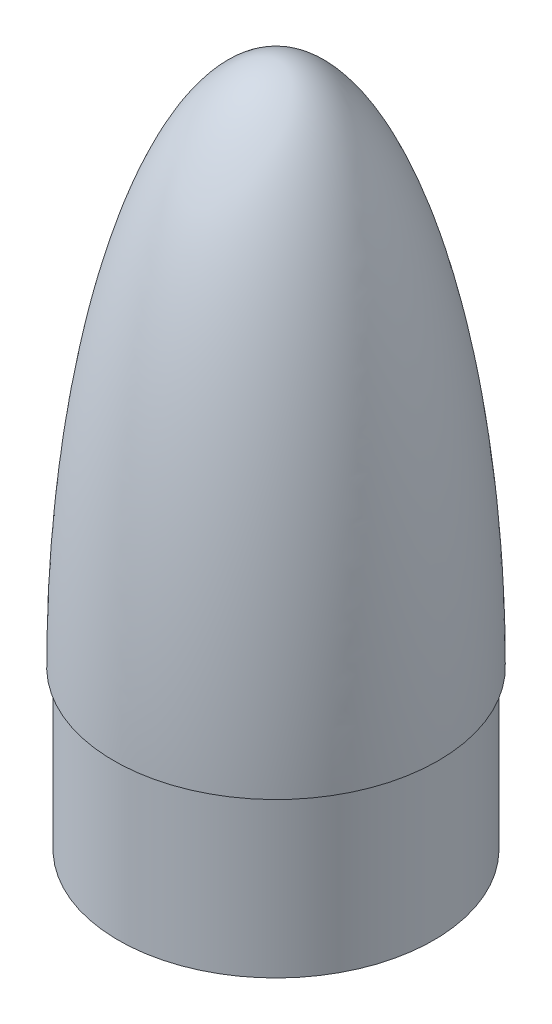
SolidWorks part; units mm, degrees
material "ABS"
ref_plane "Front Plane" through (0, 0, 0) normal (0, 0, 1) x (1, 0, 0)
ref_plane "Top Plane" through (0, 0, 0) normal (0, 1, 0) x (1, 0, 0)
ref_plane "Right Plane" through (0, 0, 0) normal (1, 0, 0) x (0, 0, -1)
sketch "Sketch1" plane through (0, 0, 0) normal (0, 0, 1) x (1, 0, 0)
  line L0 (0, 254) -> (0, 0) construction
  line L1 (78.359, 0) -> (0, 0)
  line L2 (0, 0) -> (0, 254)
  spline S0 degree 4 poles (77.9662, -25.3999) (78.0154, -23.8095) (78.1056, -20.6522) (78.1976, -16.6458) (78.2773, -11.9379) (78.3233, -7.8867) (78.3478, -4.9036) (78.3593, -1.4843) (78.3601, 0.7911) (78.3527, 3.5863) (78.3388, 5.9889) (78.318, 8.3522) (78.2903, 10.7456) (78.247, 13.7314) (78.1811, 17.3117) (78.0839, 21.4904) (77.9448, 26.2641) (77.7777, 31.0376) (77.5823, 35.8096) (77.3585, 40.5805) (77.0429, 46.5423) (76.6791, 52.5014) (76.2664, 58.4574) (75.8041, 64.4096) (75.404, 69.1689) (74.8656, 75.1148) (74.1574, 82.244) (73.2383, 90.5517) (72.0557, 100.0308) (70.7355, 109.4917) (69.2709, 118.9313) (67.25, 130.6999) (64.5017, 144.7638) (61.3086, 158.736) (57.591, 172.5772) (53.383, 186.2759) (49.2387, 198.0448) (44.4832, 209.5873) (38.9429, 220.7192) (34.2562, 228.6936) (29.8187, 235.0954) (25.6242, 240.1829) (21.9789, 243.9262) (18.5702, 246.8595) (15.4743, 249.0762) (12.5634, 250.7857) (9.7723, 252.0835) (7.0631, 253.0286) (4.2754, 253.6868) (2.188, 253.9399) (0.7672, 253.9999) (0, 254) knots 0 0 0 0 0 0.020823 0.041645 0.052056 0.062468 0.072879 0.08329 0.09112 0.098949 0.106779 0.114608 0.122438 0.130267 0.145926 0.161585 0.177244 0.192903 0.208562 0.224221 0.23988 0.271198 0.286857 0.302516 0.318175 0.333834 0.365152 0.39647 0.427788 0.459106 0.490424 0.521742 0.584379 0.647015 0.678333 0.709651 0.772287 0.810589 0.841907 0.872608 0.893486 0.912628 0.928287 0.941045 0.952387 0.962498 0.972496 0.981349 0.98995 1 1 1 1 1 construction
  spline S1 degree 4 poles (78.359, 0) (78.359, 0.5473) (78.3578, 1.6496) (78.3527, 3.5863) (78.3388, 5.9889) (78.318, 8.3522) (78.2903, 10.7456) (78.247, 13.7314) (78.1811, 17.3117) (78.0839, 21.4904) (77.9448, 26.2641) (77.7777, 31.0376) (77.5823, 35.8096) (77.3585, 40.5805) (77.0429, 46.5423) (76.6791, 52.5014) (76.2664, 58.4574) (75.8041, 64.4096) (75.404, 69.1689) (74.8656, 75.1148) (74.1574, 82.244) (73.2383, 90.5517) (72.0557, 100.0308) (70.7355, 109.4917) (69.2709, 118.9313) (67.25, 130.6999) (64.5017, 144.7638) (61.3086, 158.736) (57.591, 172.5772) (53.383, 186.2759) (49.2387, 198.0448) (44.4832, 209.5873) (38.9429, 220.7192) (34.2562, 228.6936) (29.8187, 235.0954) (25.6242, 240.1829) (21.9789, 243.9262) (18.5702, 246.8595) (15.4743, 249.0762) (12.5634, 250.7857) (9.7723, 252.0835) (7.0631, 253.0286) (4.2754, 253.6868) (2.188, 253.9399) (0.7672, 253.9999) (0, 254) knots 0.08329 0.08329 0.08329 0.08329 0.08329 0.09112 0.098949 0.106779 0.114608 0.122438 0.130267 0.145926 0.161585 0.177244 0.192903 0.208562 0.224221 0.23988 0.271198 0.286857 0.302516 0.318175 0.333834 0.365152 0.39647 0.427788 0.459106 0.490424 0.521742 0.584379 0.647015 0.678333 0.709651 0.772287 0.810589 0.841907 0.872608 0.893486 0.912628 0.928287 0.941045 0.952387 0.962498 0.972496 0.981349 0.98995 1 1 1 1 1
revolve "Revolve1" add sketch "Sketch1" angle 360 about L0
sketch "Sketch2" plane through (0, 0, 0) normal (0, -1, 0) x (1, 0, 0)
  circle A0 centre (0, 0) radius 76.2
extrude "Boss-Extrude1" add sketch "Sketch2" along normal blind 76.2
ref_axis "Axis1" through (0, 270.51, 0) along (0, -1, 0)
sketch "Sketch4" plane through (0, 0, 0) normal (0, 1, 0) x (1, 0, 0)
  line L0 (76.2, 0) -> (-78.359, 0) construction
  line L1 (0, -78.359) -> (0, 90.3851) construction
  circle A0 centre (0, 0) radius 76.2 construction
  circle A1 centre (0, 0) radius 78.359 construction
  circle A2 centre (48.26, 0) radius 17.78
  circle A3 centre (0, -48.26) radius 17.78
  circle A4 centre (-48.26, 0) radius 17.78
  circle A5 centre (0, 48.26) radius 17.78
  point P20 (0, 0)
  point P43 (0, 0.8087)
  dimension "D2" = 35.56
  dimension "D1" = 48.26
  dimension "D3" = 4
extrude "Cut-Extrude1" cut sketch "Sketch4" along normal blind 96.52
sketch "Sketch5" plane through (0, 0, 0) normal (0, 1, 0) x (1, 0, 0)
  line L0 (-83.8326, 0) -> (109.4642, 0) construction
  line L1 (0, 82.5318) -> (0, -82.1463) construction
  circle A0 centre (20.32, 0) radius 8.255
  circle A1 centre (10.16, -17.5976) radius 8.255
  circle A2 centre (-10.16, -17.5976) radius 8.255
  circle A3 centre (-20.32, 0) radius 8.255
  circle A4 centre (-10.16, 17.5976) radius 8.255
  circle A5 centre (10.16, 17.5976) radius 8.255
  point P20 (0, 0)
  dimension "D2" = 16.51
  dimension "D1" = 20.32
  dimension "D3" = 6
extrude "Cut-Extrude2" cut sketch "Sketch5" along normal blind 119.38 from offset 106.68
sketch "Sketch6" plane through (0, 0, 0) normal (0, 0, 1) x (1, 0, 0)
  line L0 (-30.48, 96.52) -> (-48.26, 117.7094)
  line L1 (-48.26, 96.52) -> (-48.26, 0) construction
  line L2 (-66.04, 96.52) -> (-30.48, 96.52) construction
  line L3 (-48.26, 117.7094) -> (-48.26, 96.52)
  line L4 (-48.26, 96.52) -> (-30.48, 96.52)
  dimension "D1" = 50
revolve "Cut-Revolve2" cut sketch "Sketch6" angle 360 about axis through (-48.26, 96.52, 0) along (0, -1, 0)
sketch "Sketch7" plane through (0, 0, 0) normal (0, 0, 1) x (1, 0, 0)
  line L0 (17.78, 96.52) -> (0, 117.7094)
  line L1 (0, 270.51) -> (0, -92.71) construction
  line L2 (-17.78, 96.52) -> (17.78, 96.52) construction
  line L3 (0, 117.7094) -> (0, 96.52)
  line L4 (0, 96.52) -> (17.78, 96.52)
  dimension "D1" = 50
ref_plane "Plane1" through (0, 0, 48.26) normal (0, 0, 1) x (1, 0, 0)
sketch "Sketch8" plane through (0, 0, 48.26) normal (0, 0, 1) x (1, 0, 0)
  line L0 (0, 96.52) -> (17.78, 96.52)
  line L1 (17.78, 96.52) -> (0, 117.7094)
  line L2 (0, 117.7094) -> (0, 96.52)
revolve "Cut-Revolve4" cut sketch "Sketch8" angle 360 about axis through (0, 96.52, 48.26) along (0, -1, 0)
sketch "Sketch9" plane through (0, 0, 0) normal (0, 0, 1) x (1, 0, 0)
  line L0 (48.26, 96.52) -> (66.04, 96.52)
  line L1 (30.48, 96.52) -> (66.04, 96.52) construction
  line L2 (66.04, 96.52) -> (48.26, 117.7094)
  line L3 (48.26, 96.52) -> (48.26, 0) construction
  line L4 (48.26, 117.7094) -> (48.26, 96.52)
  dimension "D1" = 50
revolve "Cut-Revolve5" cut sketch "Sketch9" angle 360 about axis through (48.26, 96.52, 0) along (0, -1, 0)
ref_plane "Plane2" through (0, 0, -48.26) normal (0, 0, 1) x (1, 0, 0)
sketch "Sketch11" plane through (0, 0, -48.26) normal (0, 0, 1) x (1, 0, 0)
  line L0 (0, 96.52) -> (17.78, 96.52)
  line L1 (17.78, 96.52) -> (-17.78, 96.52) construction
  line L2 (17.78, 96.52) -> (0, 117.7094)
  line L3 (0, 117.7094) -> (0, 96.52)
revolve "Cut-Revolve6" cut sketch "Sketch11" angle 360 about axis through (0, 96.52, -48.26) along (0, -1, 0)
sketch "Sketch12" plane through (0, 0, 0) normal (0, 0, 1) x (1, 0, 0)
  line L0 (-20.32, 226.06) -> (-12.065, 226.06)
  line L1 (-28.575, 226.06) -> (-12.065, 226.06) construction
  line L2 (-12.065, 226.06) -> (-20.32, 235.8979)
  line L3 (-20.32, 226.06) -> (-20.32, 106.68) construction
  line L4 (-20.32, 235.8979) -> (-20.32, 226.06)
  dimension "D1" = 50
revolve "Cut-Revolve7" cut sketch "Sketch12" angle 360 about axis through (-20.32, 226.06, 0) along (0, -1, 0)
sketch "Sketch14" plane through (0, 0, 0) normal (0, 0, 1) x (1, 0, 0)
  line L0 (20.32, 226.06) -> (28.575, 226.06)
  line L1 (12.065, 226.06) -> (28.575, 226.06) construction
  line L2 (28.575, 226.06) -> (20.32, 235.8979)
  line L3 (20.32, 226.06) -> (20.32, 106.68) construction
  line L4 (20.32, 235.8979) -> (20.32, 226.06)
  dimension "D1" = 50
revolve "Cut-Revolve8" cut sketch "Sketch14" angle 360 about L4
ref_plane "Plane3" through (0, 0, 17.5976) normal (0, 0, 1) x (1, 0, 0)
sketch "Sketch15" plane through (0, 0, 17.5976) normal (0, 0, 1) x (1, 0, 0)
  line L0 (-10.16, 226.06) -> (-1.905, 226.06)
  line L1 (-18.415, 226.06) -> (-1.905, 226.06) construction
  line L2 (-1.905, 226.06) -> (-10.16, 235.8979)
  line L3 (-10.16, 226.06) -> (-10.16, 106.68) construction
  line L4 (-10.16, 235.8979) -> (-10.16, 226.06)
  dimension "D1" = 50
revolve "Cut-Revolve9" cut sketch "Sketch15" angle 360 about axis through (-10.16, 226.06, 17.5976) along (0, -1, 0)
sketch "Sketch16" plane through (0, 0, 17.5976) normal (0, 0, 1) x (1, 0, 0)
  line L0 (10.16, 226.06) -> (18.415, 226.06)
  line L1 (1.905, 226.06) -> (18.415, 226.06) construction
  line L2 (18.415, 226.06) -> (10.16, 235.8979)
  line L3 (10.16, 226.06) -> (10.16, 106.68) construction
  line L4 (10.16, 235.8979) -> (10.16, 226.06)
  dimension "D1" = 50
revolve "Cut-Revolve10" cut sketch "Sketch16" angle 360 about L4
ref_plane "Plane4" through (0, 0, -17.5976) normal (0, 0, 1) x (1, 0, 0)
sketch "Sketch17" plane through (0, 0, -17.5976) normal (0, 0, 1) x (1, 0, 0)
  line L0 (10.16, 226.06) -> (18.415, 226.06)
  line L1 (18.415, 226.06) -> (1.905, 226.06) construction
  line L2 (18.415, 226.06) -> (10.16, 235.8979)
  line L3 (10.16, 235.8979) -> (10.16, 226.06)
revolve "Cut-Revolve11" cut sketch "Sketch17" angle 360 about L3
sketch "Sketch18" plane through (0, 0, -17.5976) normal (0, 0, 1) x (1, 0, 0)
  line L0 (-10.16, 226.06) -> (-1.905, 226.06)
  line L1 (-1.905, 226.06) -> (-18.415, 226.06) construction
  line L2 (-1.905, 226.06) -> (-10.16, 235.8979)
  line L3 (-10.16, 235.8979) -> (-10.16, 226.06)
revolve "Cut-Revolve12" cut sketch "Sketch18" angle 360 about L3
sketch "Sketch19" plane through (0, 0, 0) normal (0, 1, 0) x (1, 0, 0)
  circle A0 centre (0, 0) radius 15.24
  dimension "D1" = 30.48
extrude "Cut-Extrude3" cut sketch "Sketch19" along normal blind 101.6 from offset 25.4 offset against normal yes
sketch "Sketch20" plane through (0, 0, 0) normal (0, 0, 1) x (1, 0, 0)
  line L5 (0, 76.2) -> (15.24, 76.2)
  line L6 (-15.24, 76.2) -> (15.24, 76.2) construction
  line L7 (15.24, 76.2) -> (0, 94.3623)
  line L8 (0, 270.51) -> (0, -92.71) construction
  line L9 (0, 94.3623) -> (0, 76.2)
  dimension "D1" = 50
revolve "Cut-Revolve13" cut sketch "Sketch20" angle 360 about axis through (0, 270.51, 0) along (0, -1, 0)
sketch "Sketch21" plane through (0, -76.2, 0) normal (0, -1, 0) x (1, 0, 0)
  line L1 (-31.75, 25.4) -> (19.05, 25.4) construction
  line L2 (-31.75, 25.4) -> (-31.75, -25.4) construction
  line L3 (-31.75, -25.4) -> (19.05, -25.4) construction
  line L4 (19.05, 25.4) -> (19.05, -25.4) construction
  circle A0 centre (-44.163, 0) radius 2.54
  circle A1 centre (0, 37.813) radius 2.54
  circle A2 centre (31.463, 0) radius 2.54
  circle A3 centre (0, -37.813) radius 2.54
  point P12 (-31.75, 0)
  point P14 (19.05, 0)
  dimension "D1" = 50.8
  dimension "D3" = 5.08
  dimension "D5" = 12.413
  dimension "D8" = 5.08
  dimension "D9" = 5.08
  dimension "D10" = 5.08
  dimension "D2" = 50.8
  dimension "D4" = 12.413
  dimension "D6" = 12.413
  dimension "D7" = 12.413
extrude "Cut-Extrude4" cut sketch "Sketch21" against normal blind 6.35
sketch "Sketch22" plane through (0, -76.2, 0) normal (0, -1, 0) x (1, 0, 0)
  line L0 (-71.5421, -6.5577) -> (-6.5577, 71.5421) construction
  line L1 (-6.5577, 71.5421) -> (71.5421, 6.5577) construction
  line L2 (71.5421, 6.5577) -> (6.5577, -71.5421) construction
  line L3 (6.5577, -71.5421) -> (-71.5421, -6.5577) construction
  line L4 (0, -37.813) -> (31.463, 0) construction
  circle A0 centre (-32.4922, -39.0499) radius 3
  circle A1 centre (-39.0499, 32.4922) radius 3
  circle A2 centre (32.4922, 39.0499) radius 3
  circle A3 centre (39.0499, -32.4922) radius 3
  dimension "D6" = 6
  dimension "D7" = 6
  dimension "D8" = 6
  dimension "D9" = 6
  dimension "D1" = 101.6
  dimension "D2" = 101.6
  dimension "D3" = 50.8
  dimension "D4" = 50.8
  dimension "D5" = 90
extrude "Cut-Extrude5" cut sketch "Sketch22" against normal blind 12.7
sketch "Sketch3" plane through (0, 0, 0) normal (0, 0, 1) x (1, 0, 0)
  line L0 (0, 0) -> (50.6956, 0)
  line L1 (-76.2, 0) -> (76.2, 0) construction
  line L2 (0, 0) -> (0, 122.511)
  line L3 (0, 270.51) -> (0, -92.71) construction
  arc A0 (50.6956, 0) -> (0, 122.511) centre (-122.6821, 0) ccw
revolve "Cut-Revolve1" cut sketch "Sketch3" angle 360 about axis through (0, 270.51, 0) along (0, -1, 0)
equation "\"Bodytube_OD\"= 6.17in"
equation "\"Bodytube_ID\"= 5.998in"
equation "\"R\"= \"Bodytube_ID\" / 2"
equation "\"L\"= 30in"
